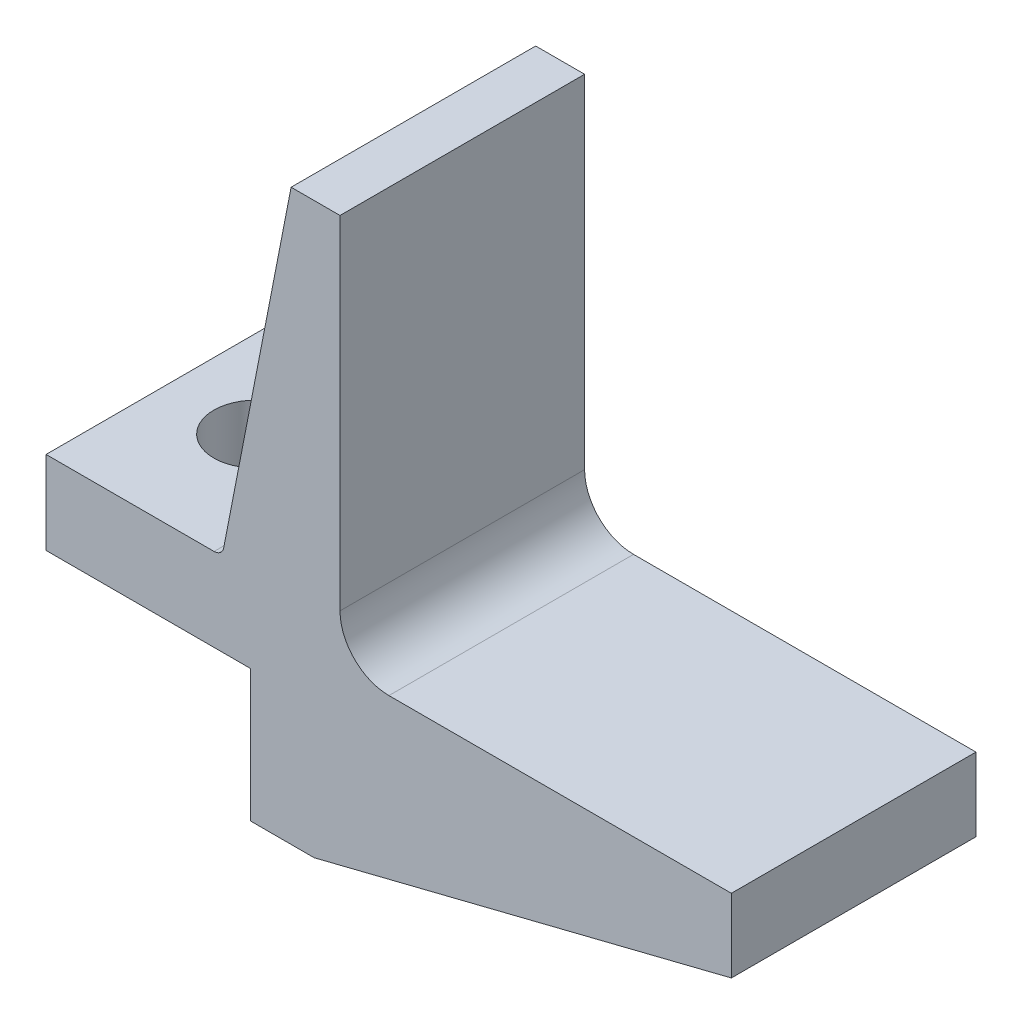
SolidWorks part; units mm, degrees
other "Markup1"
sketch "Sketch7" plane through (-38.1608, 50.8, 31.75) normal (-0.1424, 0.1459, 0.979) x (0.9898, 0.0098, 0.1425)
material "7075-T6 (SN)"
ref_plane "Front Plane" through (0, 0, 0) normal (0, 0, 1) x (1, 0, 0)
ref_plane "Top Plane" through (0, 0, 0) normal (0, 1, 0) x (1, 0, 0)
ref_plane "Right Plane" through (0, 0, 0) normal (1, 0, 0) x (0, 0, -1)
sketch "Sketch1" plane through (0, 0, 0) normal (0, 0, 1) x (1, 0, 0)
  line L0 (0, 0) -> (50.8, 0)
  line L1 (50.8, 0) -> (50.8, -9.525)
  line L2 (-11.6178, -5.9413) -> (-38.1608, -5.9413)
  line L3 (-38.1608, -5.9413) -> (-38.1608, 4.8537)
  line L4 (-38.1608, 4.8537) -> (-15.3008, 4.8537)
  line L5 (-15.3008, 4.8537) -> (-6.35, 50.8)
  line L6 (-6.35, 50.8) -> (0, 50.8)
  line L7 (0, 50.8) -> (0, 0)
  line L8 (-11.6178, -5.9413) -> (-11.6178, -23.0863)
  line L9 (-11.6178, -23.0863) -> (-3.3628, -23.0863)
  line L10 (-3.3628, -23.0863) -> (50.8, -9.525)
  dimension "D1" = 50.8
  dimension "D2" = 50.8
  dimension "D3" = 9.525
  dimension "D4" = 38.1608
  dimension "D5" = 6.35
  dimension "D6" = 22.86
  dimension "D7" = 26.543
  dimension "D8" = 10.795
  dimension "D9" = 17.145
  dimension "D10" = 8.255
  dimension "D11" = 4.8537
extrude "Boss-Extrude1" add sketch "Sketch1" along normal blind 31.75
hole_wizard "3/8 (0.375) Diameter Hole1" positions "Sketch8" profile "Sketch3" hole size "3/8" standard "ANSI Inch" end condition through all
sketch "Sketch8" plane through (0, 4.8537, 0) normal (0, 1, 0) x (1, 0, 0)
  line L1 (-38.1608, -31.75) -> (-38.1608, 0) construction
  point P0 (-26.8578, -15.875)
  point P8 (-38.1608, -15.875)
  dimension "D1" = 11.303
sketch "Sketch3" plane through (-26.8578, 4.8537, 15.875) normal (1, 0, 0) x (0, 0, 1)
  line L0 (0, 0) -> (0, 27.94)
  line L1 (0, 27.94) -> (5.3975, 27.94)
  line L2 (5.3975, 27.94) -> (5.3975, 0)
  line L5 (5.3975, 0) -> (0, 0)
  line L11 (0, -6.35) -> (0, 107.95) construction
  dimension "Thru Hole Dia." = 10.795
  dimension "Thru Hole Depth" = 27.94
fillet "Fillet1" radius 1.27 1 edges at (-15.3008, 4.8537, 15.875)
fillet "Fillet2" radius 6.35 1 edges at (0, 0, 15.875)
